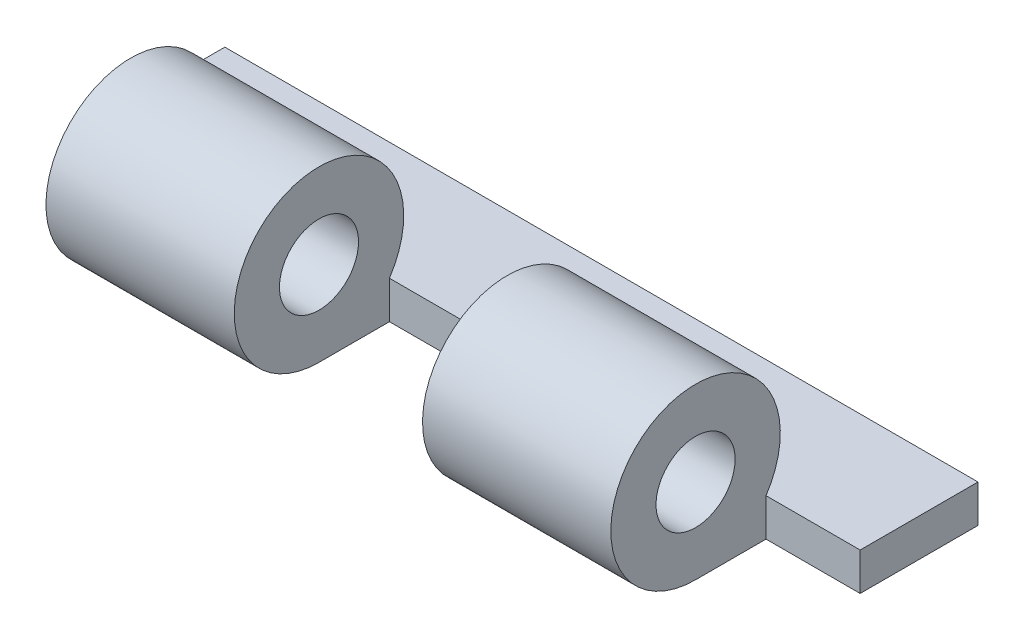
SolidWorks part; units mm, degrees
ref_plane "Ebene vorne" through (0, 0, 0) normal (0, 0, 1) x (1, 0, 0)
ref_plane "Ebene oben" through (0, 0, 0) normal (0, 1, 0) x (1, 0, 0)
ref_plane "Ebene rechts" through (0, 0, 0) normal (1, 0, 0) x (0, 0, -1)
sketch "Skizze2" plane through (0, 0, 0) normal (0, 1, 0) x (1, 0, 0)
  line L1 (-7.5, 2.5) -> (7.5, 2.5)
  line L2 (-7.5, 2.5) -> (-7.5, -2.5)
  line L3 (-7.5, -2.5) -> (7.5, -2.5)
  line L4 (7.5, 2.5) -> (7.5, -2.5)
  line L5 (-7.5, 2.5) -> (7.5, -2.5) construction
  line L6 (-7.5, -2.5) -> (7.5, 2.5) construction
  point P0 (0, 0)
  dimension "D1" = 15
  dimension "D2" = 5
extrude "Aufsatz-Linear austragen1" add sketch "Skizze2" along normal blind 1
sketch "Skizze3" plane through (7.5, 0, 0) normal (1, 0, 0) x (0, 0, -1)
  circle A0 centre (-2.5, 2.25) radius 2.25
  circle A1 centre (-2.5, 2.25) radius 1.05
  dimension "D1" = 2.1
  dimension "D2" = 4.5
extrude "Aufsatz-Linear austragen2" add sketch "Skizze3" against normal up to surface (15 mm away) up to face at (-7.5, 0.5, 0)
ref_plane "Tangential Ebene" through (0, 0, 0.25) normal (0, 0, -1) x (-1, 0, 0)
sketch "Skizze5" plane through (7.5, 0, 0) normal (1, 0, 0) x (0, 0, -1)
  line L0 (-0.6292, 1) -> (-0.6292, 0)
  line L1 (-0.6292, 0) -> (-2.5, 0)
  line L3 (2.5, 1) -> (-0.6292, 1)
  line L4 (-2.5, 0) -> (2.5, 0)
  line L5 (2.5, 0) -> (2.5, 1)
  line L6 (2.5, 1) -> (-0.6292, 1) construction
  line L7 (-2.5, 0) -> (2.5, 0) construction
  line L8 (2.5, 0) -> (2.5, 1) construction
  arc A1 (-0.6292, 1) -> (-2.5, 0) centre (-2.5, 2.25) ccw
  arc A2 (-0.6292, 1) -> (-2.5, 0) centre (-2.5, 2.25) ccw
  dimension "D1" = 0
extrude "Schnitt-Linear austragen1" cut sketch "Skizze5" against normal blind 5 from offset 5 offset against normal yes
ref_plane "Spiegelebene" through (0, 0, 0) normal (1, 0, 0) x (0, 0, -1)
sketch "Skizze7" plane through (7.5, 0, 0) normal (1, 0, 0) x (0, 0, -1)
  line L1 (-0.6292, 1) -> (2.5, 1)
  line L2 (-0.6292, 1) -> (-0.6292, 0)
  line L3 (-0.6292, 0) -> (2.5, 0)
  line L4 (2.5, 1) -> (2.5, 0)
extrude "Aufsatz-Linear austragen3" add sketch "Skizze7" along normal blind 2.5
mirror "Spiegeln1" about plane through (0, 0, 0) normal (1, 0, 0) of "Aufsatz-Linear austragen3"
